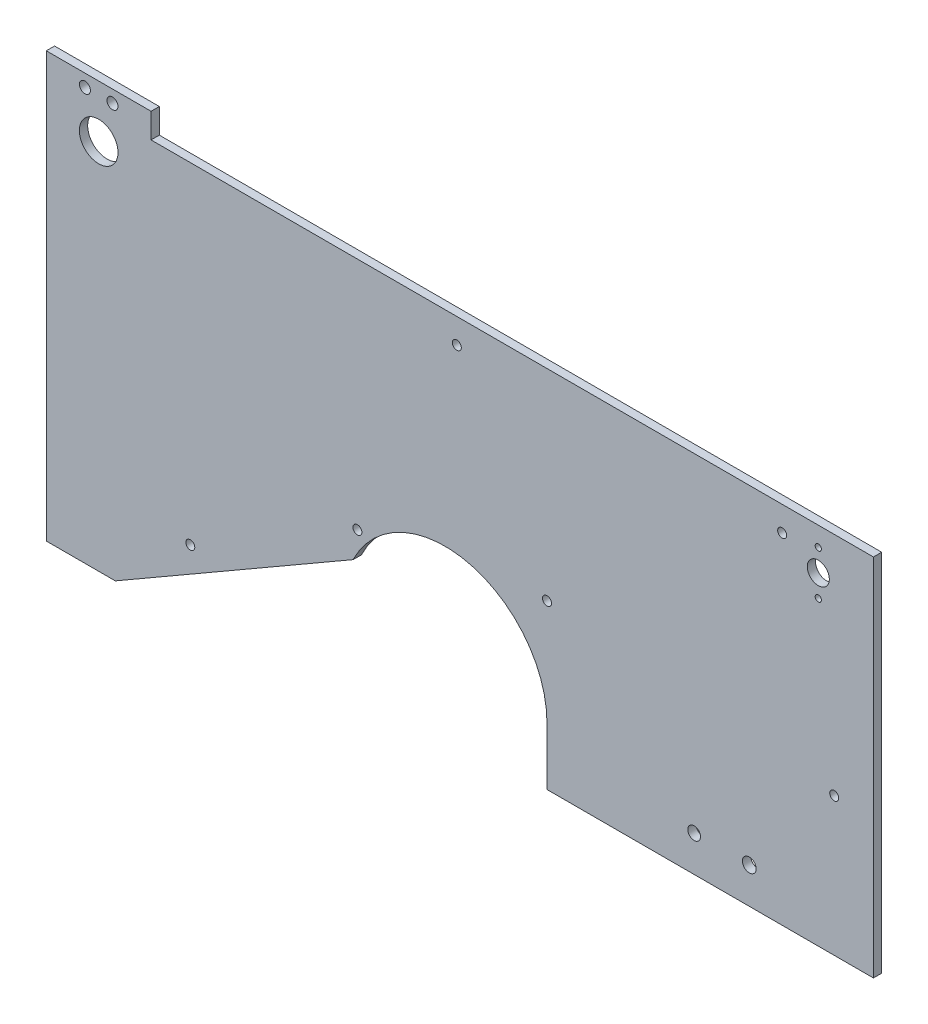
SolidWorks part; units mm, degrees
ref_plane "Front Plane" through (0, 0, 0) normal (0, 0, 1) x (1, 0, 0)
ref_plane "Top Plane" through (0, 0, 0) normal (0, 1, 0) x (1, 0, 0)
ref_plane "Right Plane" through (0, 0, 0) normal (1, 0, 0) x (0, 0, -1)
sketch "Sketch2" plane through (0, 0, 0) normal (0, 0, 1) x (1, 0, 0)
  line L0 (25.0304, 0) -> (111.2865, 49.8)
  line L1 (0, 0) -> (25.0304, 0)
  line L2 (0, 0) -> (0, 154)
  line L4 (300, 0) -> (300, 145)
  line L5 (181.6, 33.7) -> (181.6, 0)
  line L6 (181.6, 0) -> (300, 0)
  line L7 (19, 135) -> (19, 164.3674) construction
  line L11 (38, 145) -> (300, 145)
  line L12 (0, 154) -> (19, 154)
  line L13 (19, 154) -> (38, 154)
  line L14 (38, 154) -> (38, 145)
  line L15 (19, 135) -> (50019, 135) construction
  line L20 (19, 135) -> (19, -49865) construction
  circle A0 centre (19, 135) radius 7
  arc A1 (181.6, 33.7) -> (111.2865, 49.8) centre (144.6, 33.7) ccw
  circle A2 centre (14, 149.5) radius 2
  circle A3 centre (24, 149.5) radius 2
  point P19 (19, 154)
  dimension "D3" = 135
  dimension "D4" = 19
  dimension "D5" = 14
  dimension "D6" = 74
  dimension "D7" = 155.4
  dimension "D8" = 33.7
  dimension "D13" = 4
  dimension "D14" = 5
  dimension "D15" = 14.5
  dimension "D1" = 300
  dimension "D2" = 154
  dimension "D9" = 30
  dimension "D10" = 99.6
  dimension "D11" = 19
  dimension "D12" = 145
  dimension "D16" = 9
extrude "Boss-Extrude2" add sketch "Sketch2" along normal blind 3
sketch "Sketch3" plane through (0, 0, 3) normal (0, 0, 1) x (1, 0, 0)
  line L0 (300, 0) -> (300, 145) construction
  line L1 (181.6, 0) -> (300, 0)
  line L2 (181.6, 0) -> (181.6, 12.75)
  line L3 (181.6, 12.75) -> (300, 12.75)
  line L4 (300, 0) -> (300, 12.75)
  dimension "D1" = 12.75
extrude "Cut-Extrude1" cut sketch "Sketch3" against normal through all
sketch "Sketch4" plane through (0, 0, 3) normal (0, 0, 1) x (1, 0, 0)
  line L0 (19, 135) -> (19, -49865) construction
  line L1 (19, 135) -> (-49981, 135) construction
sketch "Sketch5" plane through (0, 0, 3) normal (0, 0, 1) x (1, 0, 0)
  line L0 (300, 12.75) -> (300, 145) construction
  line L1 (300, 12.75) -> (181.6, 12.75) construction
  line L2 (300, 145) -> (38, 145) construction
  line L3 (0, 154) -> (0, 0) construction
  line L4 (0, 0) -> (25.0304, 0) construction
  circle A0 centre (254.98, 25.75) radius 2.5
  circle A1 centre (234.98, 25.75) radius 2.3061
  circle A2 centre (280, 130) radius 4
  circle A3 centre (280, 138) radius 1.125
  circle A4 centre (280, 122) radius 1.125
  circle A7 centre (285.78, 62.92) radius 1.625
  circle A8 centre (181.6, 72.03) radius 1.625
  circle A9 centre (52.23, 24.91) radius 1.625
  circle A10 centre (112.84, 59.93) radius 1.625
  circle A11 centre (266.895, 135.995) radius 1.625
  circle A12 centre (148.895, 135.995) radius 1.625
  dimension "D1" = 45.02
  dimension "D2" = 13
  dimension "D3" = 20
  dimension "D4" = 13
  dimension "D5" = 4.6121
  dimension "D6" = 5
  dimension "D7" = 8
  dimension "D8" = 15
  dimension "D9" = 2.25
  dimension "D10" = 8
  dimension "D11" = 8
  dimension "D12" = 2.25
  dimension "D13" = 20
  dimension "D14" = 20
  dimension "D15" = 20
  dimension "D16" = 82.08
  dimension "D17" = 3.25
  dimension "D18" = 14.22
  dimension "D19" = 72.97
  dimension "D20" = 3.25
  dimension "D21" = 118.4
  dimension "D22" = 3.25
  dimension "D23" = 52.23
  dimension "D24" = 24.91
  dimension "D25" = 3.25
  dimension "D26" = 112.84
  dimension "D27" = 59.93
  dimension "D28" = 3.25
  dimension "D29" = 9.005
  dimension "D30" = 33.105
  dimension "D31" = 3.25
  dimension "D32" = 118
  dimension "D33" = 9.005
extrude "Cut-Extrude2" cut sketch "Sketch5" against normal through all
